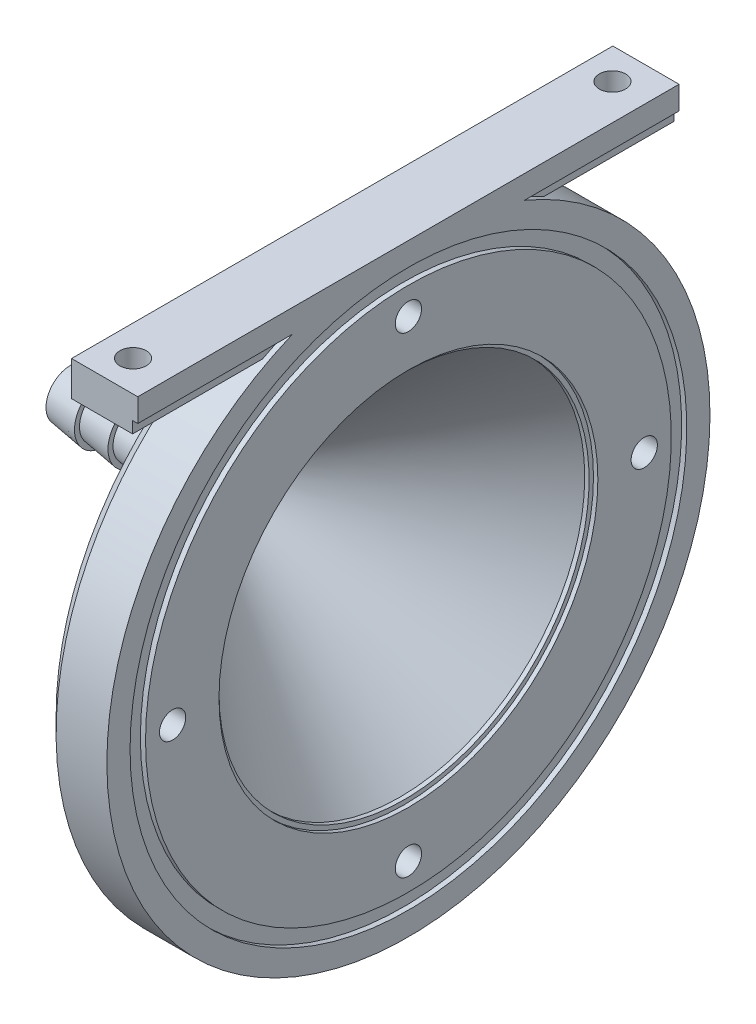
SolidWorks part; units mm, degrees
ref_plane "Front Plane" through (0, 0, 0) normal (0, 0, 1) x (1, 0, 0)
ref_plane "Top Plane" through (0, 0, 0) normal (0, 1, 0) x (1, 0, 0)
ref_plane "Right Plane" through (0, 0, 0) normal (1, 0, 0) x (0, 0, -1)
sketch "Sketch1" plane through (0, 0, 0) normal (0, 0, 1) x (1, 0, 0)
  line L0 (-801.9271, 0) -> (36107.5217, 0) construction
  line L3 (-14.0102, 3.8) -> (-14.0102, 3.15)
  line L8 (-18.3435, 1.9) -> (0, 1.9)
  line L9 (-18.3435, 1.9) -> (-18.3435, 3.15)
  line L10 (25.3752, 24.5) -> (25.3752, 39)
  line L12 (25.3752, 39) -> (16.8092, 39)
  line L16 (25.3752, 24.5) -> (24.8092, 24.5)
  line L17 (24.8092, 24.5) -> (24.8092, 23.934)
  line L18 (16.8092, 39) -> (16.8092, 23.934)
  line L20 (0, 1.9) -> (24.2432, 23.934)
  line L21 (-18.3435, 3.15) -> (-14.0102, 3.8)
  line L22 (24.2432, 23.934) -> (24.8092, 23.934)
  line L23 (-14.0102, 3.15) -> (-9.6768, 3.8)
  line L25 (-9.6768, 3.15) -> (-5.3435, 3.8)
  line L26 (-9.6768, 3.8) -> (-9.6768, 3.15)
  line L27 (-5.3435, 3.8) -> (16.8092, 23.934)
  line L28 (16.8092, 34.5) -> (25.3752, 34.5)
  line L36 (16.8092, 39) -> (25.3752, 39)
  line L38 (25.3752, 36) -> (24.7082, 36)
  line L39 (24.7082, 36) -> (24.7082, 34)
  line L40 (24.7082, 34) -> (25.3752, 34)
  dimension "D3" = 0.566
  dimension "D2" = 7.6
  dimension "D6" = 3.8
  dimension "D7" = 6.3
  dimension "D5" = 39
  dimension "D8" = 24.5
  dimension "D10" = 0.566
  dimension "D4" = 5
  dimension "D9" = 0.566
  dimension "D11" = 13
  dimension "D12" = 8.566
  dimension "D13" = 4.5
  dimension "D17" = 36
  dimension "D18" = 2
  dimension "D19" = 0.667
revolve "Revolve17" add sketch "Sketch1" angle 360 about L0 region at (11.1774, 17.6055, 0) region at (20.9869, 36.79, 0)
sketch "Sketch4" plane through (16.8092, 0, 0) normal (-1, 0, 0) x (0, 0, 1)
  circle A0 centre (0, 0) radius 30.5 construction
  circle A2 centre (0, 0) radius 39 construction
  point P3 (0, 30.5)
  point P7 (30.5, 0)
  point P12 (-30.5, 0)
  point P13 (0, -30.5)
  dimension "D1" = 8.5
hole_wizard "M3 Clearance Hole1" positions "Sketch4" profile "Sketch5" hole size "M3" standard "ISO"
sketch "Sketch5" plane through (16.8092, -30.5, 0) normal (0, 1, 0) x (0, 0, 1)
  line L0 (0, 0) -> (0, 9.5875)
  line L1 (0, 9.5875) -> (1.7, 8.566)
  line L2 (1.7, 8.566) -> (1.7, 0)
  line L5 (1.7, 0) -> (0, 0)
  line L10 (0, 9.5875) -> (-1.7, 8.566) construction
  line L11 (0, -6.35) -> (0, 107.95) construction
  dimension "Hole Dia." = 3.4
  dimension "Hole Depth" = 8.566
  dimension "Drill Angle" = 118
chamfer "Chamfer1" distance 2 angle 45 1 edges at (16.8092, 0, 39)
extrude "Boss-Extrude1" add sketch "Sketch1<11>" against normal mid plane 70 contours L18 L28 L10 L12 region at (20.9869, 36.79, 0)
sketch "Sketch1<11>" plane through (0, 0, 0) normal (0, 0, 1) x (1, 0, 0) same geometry as "Sketch1"
sketch "Sketch9" plane through (0, 34.5, 0) normal (0, -1, 0) x (-1, 0, 0)
  line L0 (-16.8092, -35) -> (-25.3752, 35) construction
  line L1 (-16.8092, -13.3697) -> (-16.8092, -35) construction
  line L2 (-16.8092, -35) -> (-24.7082, -35) construction
  line L3 (-25.3752, 35) -> (-25.3752, -18.1865) construction
  line L4 (-25.3752, 35) -> (-16.1422, 35) construction
  line L5 (-16.8092, 35) -> (-24.7082, 35) construction
  line L6 (-16.1422, 35) -> (-25.3752, -35) construction
  line L7 (-25.3752, -18.1865) -> (-25.3752, -35) construction
  line L8 (-20.7587, -35) -> (-20.7587, 35) construction
  line L9 (-4.5963, 0) -> (-25.3752, 0) construction
  line L10 (-25.3752, 39) -> (-25.3752, -39) construction
  circle A0 centre (-20.7587, -31) radius 1.7
  circle A1 centre (-20.7587, 31) radius 1.7
  dimension "D1" = 3.4
  dimension "D2" = 4
extrude "Cut-Extrude1" cut sketch "Sketch9" against normal blind 10
sketch "Sketch10" plane through (16.8092, 0, 0) normal (-1, 0, 0) x (0, 0, 1)
  line L0 (37, 0) -> (23.934, 0)
  line L1 (-23.934, 0) -> (-37, 0)
  line L2 (0, -23.934) -> (0, -37)
  circle A1 centre (0, 0) radius 23.934 construction
  point P15 (0, 30.467)
equation "\"D10@Sketch1\"=\"D3@Sketch1\""
equation "\"D9@Sketch1\"=\"D3@Sketch1\""
